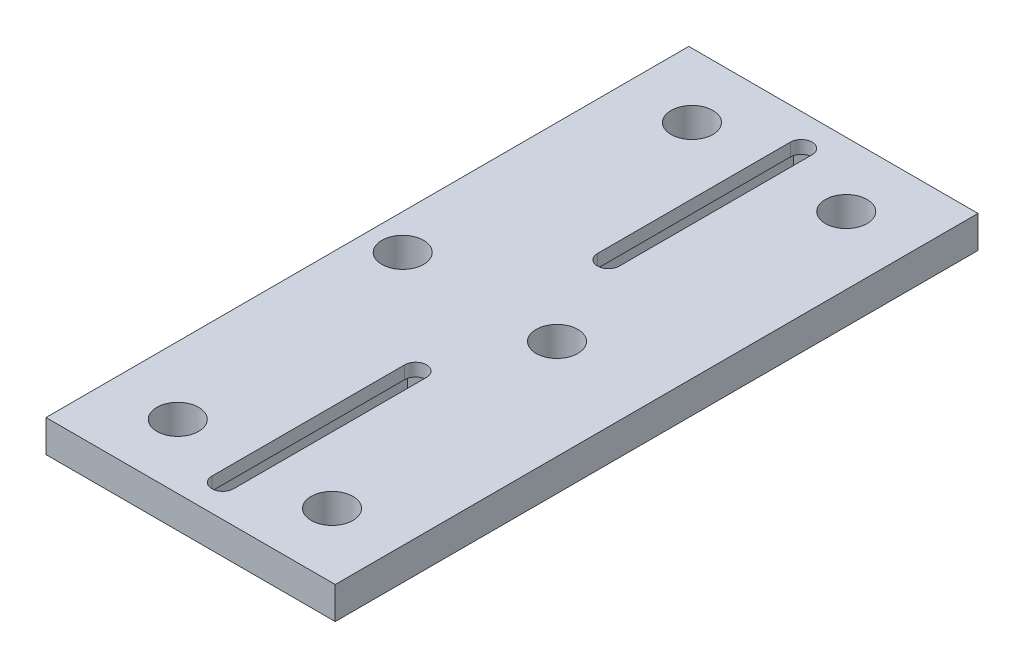
SolidWorks part; units mm, degrees
ref_plane "Front Plane" through (0, 0, 0) normal (0, 0, 1) x (1, 0, 0)
ref_plane "Top Plane" through (0, 0, 0) normal (0, 1, 0) x (1, 0, 0)
ref_plane "Right Plane" through (0, 0, 0) normal (1, 0, 0) x (0, 0, -1)
sketch "Sketch1" plane through (0, 0, 0) normal (0, 1, 0) x (1, 0, 0)
  line L1 (-12, -40) -> (12, -40) construction
  line L2 (-12, -40) -> (-12, 40) construction
  line L3 (-12, 40) -> (12, 40) construction
  line L4 (12, -40) -> (12, 40) construction
  line L5 (-12, -40) -> (12, 40) construction
  line L6 (-12, 40) -> (12, -40) construction
  line L7 (-22.5, -50) -> (22.5, -50)
  line L8 (-22.5, -50) -> (-22.5, 50)
  line L9 (-22.5, 50) -> (22.5, 50)
  line L10 (22.5, -50) -> (22.5, 50)
  line L11 (-22.5, -50) -> (22.5, 50) construction
  line L12 (-22.5, 50) -> (22.5, -50) construction
  circle A0 centre (-12, 40) radius 3.25
  circle A1 centre (12, 40) radius 3.25
  circle A2 centre (12, -40) radius 3.25
  circle A3 centre (-12, -40) radius 3.25
  circle A4 centre (7, 0) radius 3.25
  circle A5 centre (-17, 0) radius 3.25
  point P0 (0, 0)
  point P14 (0, 0)
  dimension "D3" = 6.5
  dimension "D4" = 5
  dimension "D5" = 24
  dimension "D1" = 80
  dimension "D2" = 24
  dimension "D6" = 100
  dimension "D7" = 45
extrude "Boss-Extrude1" add sketch "Sketch1" along normal blind 5
sketch "Sketch2" plane through (0, 5, 0) normal (0, 1, 0) x (1, 0, 0)
  line L0 (-1000, 0) -> (49000, 0) construction
  line L1 (0, 45) -> (0, 15) construction
  line L2 (1.7, 45) -> (1.7, 15)
  line L3 (-1.7, 45) -> (-1.7, 15)
  arc A0 (1.7, 45) -> (-1.7, 45) centre (0, 45) ccw
  arc A1 (-1.7, 15) -> (1.7, 15) centre (0, 15) ccw
  point P5 (0, 30)
  point P10 (12, 19.24)
  point P11 (0, 0)
  dimension "D3" = 1.7
  dimension "D1" = 30
  dimension "D2" = 15
extrude "Cut-Extrude1" cut sketch "Sketch2" against normal blind 2
sketch "Sketch3" plane through (0, 3, 0) normal (0, 1, 0) x (1, 0, 0)
  line L0 (2.9, 43.3257) -> (2.9, 16.6743)
  line L1 (2.9, 46.6743) -> (0, 48.3486)
  line L2 (0, 48.3486) -> (-2.9, 46.6743)
  line L3 (-2.9, 46.6743) -> (-2.9, 43.3257)
  line L4 (-2.9, 43.3257) -> (0, 41.6514)
  line L5 (0, 41.6514) -> (2.9, 43.3257)
  line L6 (2.9, 43.3257) -> (2.9, 46.6743)
  line L7 (2.9, 16.6743) -> (0, 18.3486)
  line L8 (0, 18.3486) -> (-2.9, 16.6743)
  line L9 (-2.9, 16.6743) -> (-2.9, 13.3257)
  line L10 (-2.9, 13.3257) -> (0, 11.6514)
  line L11 (0, 11.6514) -> (2.9, 13.3257)
  line L12 (2.9, 13.3257) -> (2.9, 16.6743)
  line L13 (-2.9, 43.3257) -> (-2.9, 16.6743)
  circle A0 centre (0, 45) radius 2.9 construction
  circle A1 centre (0, 15) radius 2.9 construction
  arc M3 (1.7, 45) -> (-1.7, 45) centre (0, 45) ccw
  line M4 (-1.7, 45) -> (-1.7, 15)
  arc M5 (-1.7, 15) -> (1.7, 15) centre (0, 15) ccw
  line M6 (1.7, 15) -> (1.7, 45)
  dimension "D1" = 5.8
extrude "Cut-Extrude2" cut sketch "Sketch3" against normal up to next contours L4 L5 M6 M3 M4 | L8 L7 L5 L4 M6 M4 | L7 L8 M4 M5 M6 | L4 L13 L8 M4 | L7 L0 L5 M6 | L5 L6 L1 L2 L3 L4 M4 M3 M6 | L11 L12 L7 L8 L9 L10 M6 M5 M4 region at (2.3053, 3, -30) region at (2.2593, 3, -43.0498) region at (2.8186, 3, -15) region at (0, 3, -30) region at (0, 3, -44.2462) region at (0, 3, -15.7538) region at (-2.3053, 3, -30)
mirror "Mirror1" about plane through (0, 0, 0) normal (0, 0, 1) of "Cut-Extrude2", "Cut-Extrude1"
